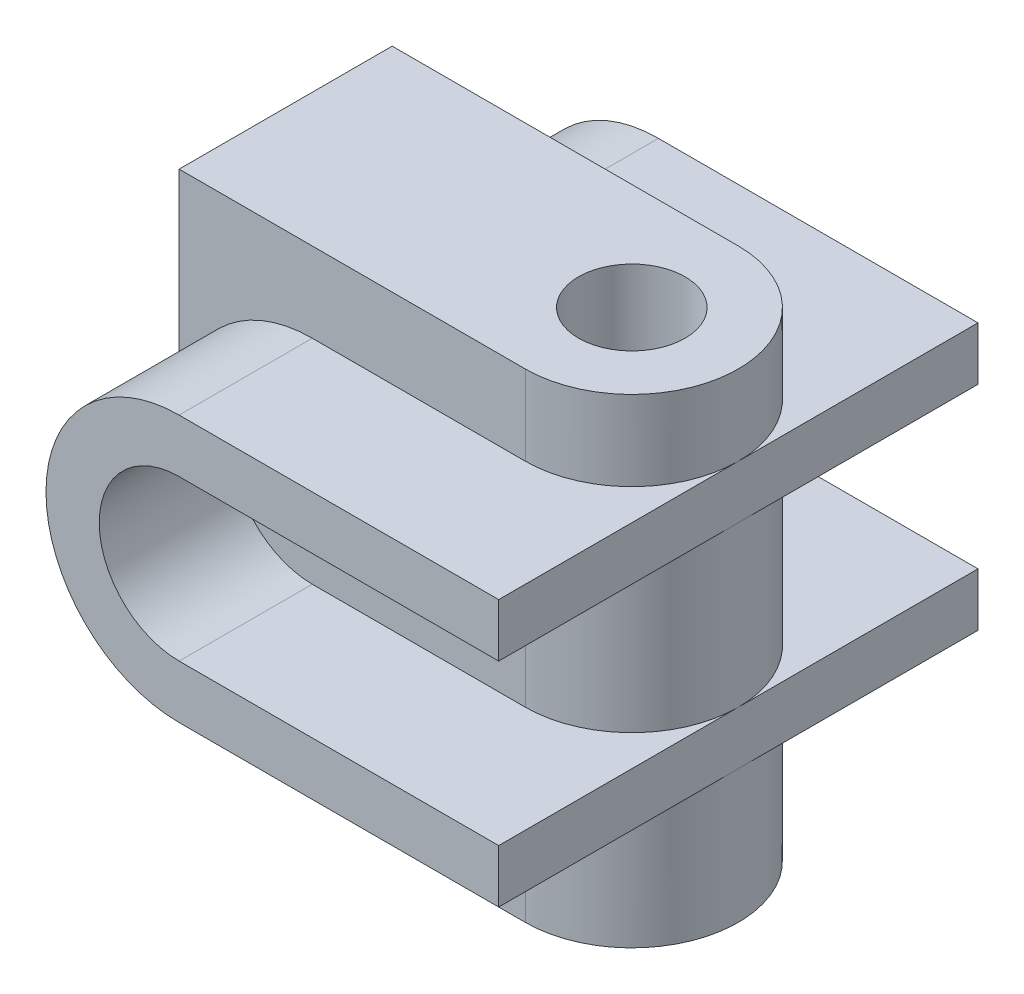
SolidWorks part; units mm, degrees
ref_plane "Front" through (0, 0, 0) normal (0, 0, 1) x (1, 0, 0)
ref_plane "Top" through (0, 0, 0) normal (0, 1, 0) x (1, 0, 0)
ref_plane "Right" through (0, 0, 0) normal (1, 0, 0) x (0, 0, -1)
other "Configuration Table"
sketch "Sketch1" plane through (0, 0, 0) normal (0, 0, 1) x (1, 0, 0)
  line L0 (0, -15) -> (-60, -15)
  line L1 (-60, -65) -> (0, -65)
  arc A0 (-60, -15) -> (-60, -65) centre (-60, -40) ccw
  dimension "D3" = 25
  dimension "D1" = 15
  dimension "D2" = 60
extrude "Extrude-Thin1" add sketch "Sketch1" along normal blind 90 thin thin type one direction reverse wall 10
sketch "Sketch2" plane through (0, 0, 0) normal (0, 1, 0) x (1, 0, 0)
  line L0 (-85, -25) -> (-85, -65)
  line L1 (-85, 0) -> (-85, -90) construction
  line L2 (-85, -65) -> (-20, -65)
  line L3 (-20, -25) -> (-85, -25)
  line L4 (0, -90) -> (0, 0) construction
  arc A0 (-20, -65) -> (-20, -25) centre (-20, -45) ccw
  circle A1 centre (-20, -45) radius 10
  dimension "D2" = 25
  dimension "D3" = 20
  dimension "D1" = 40
extrude "Boss-Extrude1" add sketch "Sketch2" against normal blind 90 separate body
combine bodies "official_combine_multi_inter" operation type add bodies to combine 101 102
